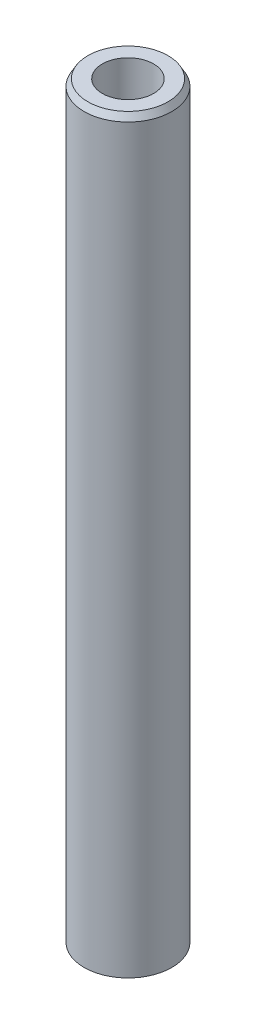
SolidWorks part; units mm, degrees
ref_plane "Front Plane" through (0, 0, 0) normal (0, 0, 1) x (1, 0, 0)
ref_plane "Top Plane" through (0, 0, 0) normal (0, 1, 0) x (1, 0, 0)
ref_plane "Right Plane" through (0, 0, 0) normal (1, 0, 0) x (0, 0, -1)
sketch "Sketch1" plane through (0, 0, 0) normal (0, 1, 0) x (1, 0, 0)
  circle A0 centre (0, 0) radius 35
  dimension "SHAFT_OD" = 70
extrude "Boss-Extrude1" add sketch "Sketch1" along normal blind 600
sketch "Sketch2" plane through (0, 0, 0) normal (0, 1, 0) x (1, 0, 0)
  circle A0 centre (0, 0) radius 20.4805
  dimension "BORE_D" = 40.9609
extrude "Cut-Extrude1" cut sketch "Sketch2" along normal through all
chamfer "Chamfer1" distance 5.2439 angle 30 2 edges at (0, 600, 35) (0, 0, 35) first distance on face at (0, 600, 35) first distance on face at (0, 0, 20.4805)
